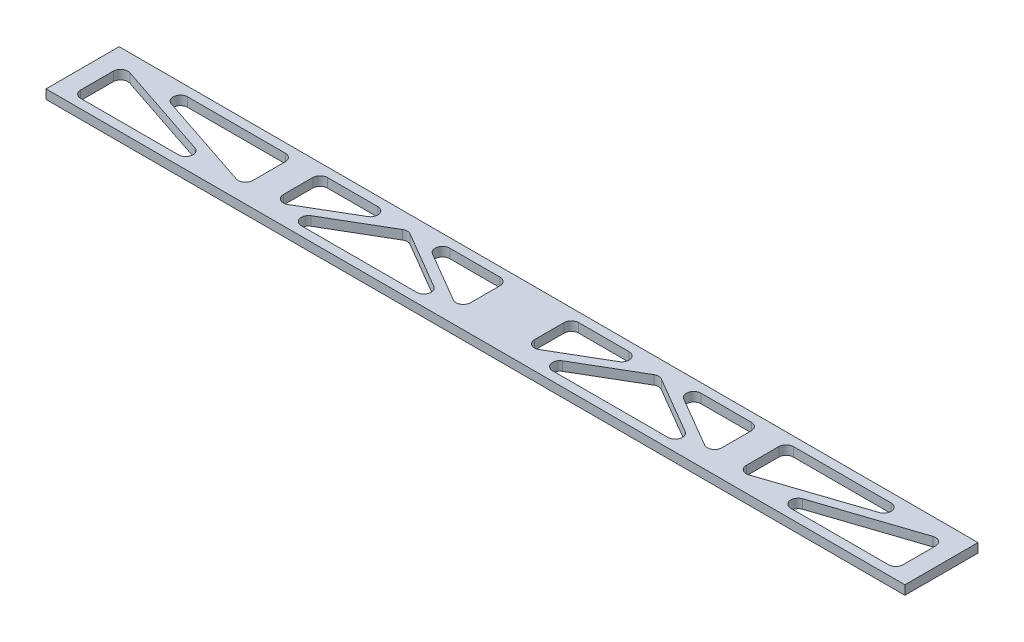
SolidWorks part; units mm, degrees
material "Balsa"
ref_plane "Front Plane" through (0, 0, 0) normal (0, 0, 1) x (1, 0, 0)
ref_plane "Top Plane" through (0, 0, 0) normal (0, 1, 0) x (1, 0, 0)
ref_plane "Right Plane" through (0, 0, 0) normal (1, 0, 0) x (0, 0, -1)
sketch "Sketch1" plane through (0, 0, 0) normal (0, 1, 0) x (1, 0, 0)
  line L1 (149.225, -12.7) -> (-149.225, -12.7)
  line L2 (149.225, -12.7) -> (149.225, 12.7)
  line L3 (149.225, 12.7) -> (-149.225, 12.7)
  line L4 (-149.225, -12.7) -> (-149.225, 12.7)
  point P0 (0, 12.7)
  point P6 (-149.225, 0)
  dimension "D1" = 25.4
  dimension "D2" = 298.45
extrude "Boss-Extrude1" add sketch "Sketch1" along normal blind 3.175
sketch "Sketch2" plane through (0, 3.175, 0) normal (0, 1, 0) x (1, 0, 0)
  line L0 (149.225, -12.7) -> (149.225, 12.7) construction
  line L2 (-149.225, 12.7) -> (-149.225, -12.7) construction
  line L4 (149.225, -12.7) -> (149.225, 12.7)
  line L6 (-149.225, 12.7) -> (-149.225, -12.7)
  line L8 (149.225, 9.525) -> (-149.225, 9.525)
  line L9 (-149.225, -9.525) -> (149.225, -9.525)
  line L10 (-142.875, 9.525) -> (-142.875, -9.525)
  line L11 (-80.9625, 9.525) -> (-80.9625, -9.525) construction
  line L12 (142.875, 9.525) -> (142.875, -9.525)
  line L13 (0, -9.525) -> (0, 9.525) construction
  line L14 (11.1125, 9.525) -> (11.1125, -9.525)
  line L15 (-11.1125, 9.525) -> (-11.1125, -9.525)
  line L16 (-85.725, 9.525) -> (-85.725, -9.525)
  line L17 (-76.2, 9.525) -> (-76.2, -9.525)
  line L18 (80.9625, 9.525) -> (80.9625, -9.525) construction
  line L19 (85.725, 9.525) -> (85.725, -9.525)
  line L20 (76.2, 9.525) -> (76.2, -9.525)
  line L21 (-76.2, -9.525) -> (-43.6562, 9.525)
  line L22 (-43.6562, 9.525) -> (-11.1125, -9.525)
  line L23 (-85.725, -9.525) -> (-142.875, 9.525)
  line L24 (11.1125, -9.525) -> (43.6562, 9.525)
  line L25 (43.6562, 9.525) -> (76.2, -9.525)
  line L26 (85.725, -9.525) -> (142.875, 9.525)
  line L27 (-85.223, -8.019) -> (-142.373, 11.031)
  line L28 (-75.398, -10.895) -> (-43.6562, 7.6855)
  line L29 (-43.6562, 7.6855) -> (-11.9145, -10.895)
  line L30 (11.9145, -10.895) -> (43.6562, 7.6855)
  line L31 (43.6562, 7.6855) -> (75.398, -10.895)
  line L32 (86.227, -11.031) -> (143.377, 8.019)
  line L33 (-86.227, -11.031) -> (-143.377, 8.019)
  line L34 (-77.002, -8.155) -> (-43.6562, 11.3645)
  line L35 (-43.6562, 11.3645) -> (-10.3105, -8.155)
  line L36 (10.3105, -8.155) -> (43.6562, 11.3645)
  line L37 (43.6562, 11.3645) -> (77.002, -8.155)
  line L38 (85.223, -8.019) -> (142.373, 11.031)
  dimension "D1" = 3.175
  dimension "D2" = 3.175
  dimension "D3" = 6.35
  dimension "D4" = 6.35
  dimension "D11" = 4.7625
  dimension "D12" = 4.7625
  dimension "D8" = 9.525
  dimension "D9" = 4.7625
  dimension "D7" = 63.5
  dimension "D10" = 63.5
  dimension "D5" = 22.225
  dimension "D6" = 11.1125
  dimension "D13" = 1.5875
  dimension "D14" = 1.5875
extrude "Cut-Extrude1" cut sketch "Sketch2" against normal through all contours L9 L33 L10 | L27 L16 L8 | L17 L34 L8 | L29 L28 L9 | L8 L35 L15 | L14 L36 L8 | L31 L30 L9 | L8 L37 L20 | L19 L38 L8 | L32 L9 L12 region at (125.4984, 3.175, 3.7328) region at (103.1016, 3.175, -3.7328) region at (66.3996, 3.175, -3.7882) region at (43.6562, 3.175, 3.7882) region at (20.9129, 3.175, -3.7882) region at (-20.9129, 3.175, -3.7882) region at (-43.6562, 3.175, 3.7882) region at (-66.3996, 3.175, -3.7882) region at (-103.1016, 3.175, -3.7328) region at (-125.4984, 3.175, 3.7328)
fillet "Fillet1" radius 2.54 30 edges at (-14.2549, 1.5875, 9.525) (-73.0576, 1.5875, 9.525) (-43.6562, 1.5875, -7.6855) (-11.1125, 1.5875, 7.6855) (-40.5138, 1.5875, -9.525) (-11.1125, 1.5875, -9.525) (-46.7987, 1.5875, -9.525) (-76.2, 1.5875, 7.6855) (-76.2, 1.5875, -9.525) (73.0576, 1.5875, 9.525) (14.2549, 1.5875, 9.525) (43.6562, 1.5875, -7.6855) (142.875, 1.5875, -7.8516) (142.875, 1.5875, 9.525) (90.7451, 1.5875, 9.525) (40.5138, 1.5875, -9.525) (11.1125, 1.5875, 7.6855) (11.1125, 1.5875, -9.525) (76.2, 1.5875, 7.6855) (46.7987, 1.5875, -9.525) (76.2, 1.5875, -9.525) (137.8549, 1.5875, -9.525) (85.725, 1.5875, 7.8516) (85.725, 1.5875, -9.525) (-137.8549, 1.5875, -9.525) (-85.725, 1.5875, 7.8516) (-85.725, 1.5875, -9.525) (-90.7451, 1.5875, 9.525) (-142.875, 1.5875, 9.525) (-142.875, 1.5875, -7.8516)
equation "\"D10@Sketch2\"=\"D7@Sketch2\""
equation "\"D6@Sketch2\"=\"D5@Sketch2\"/2"
